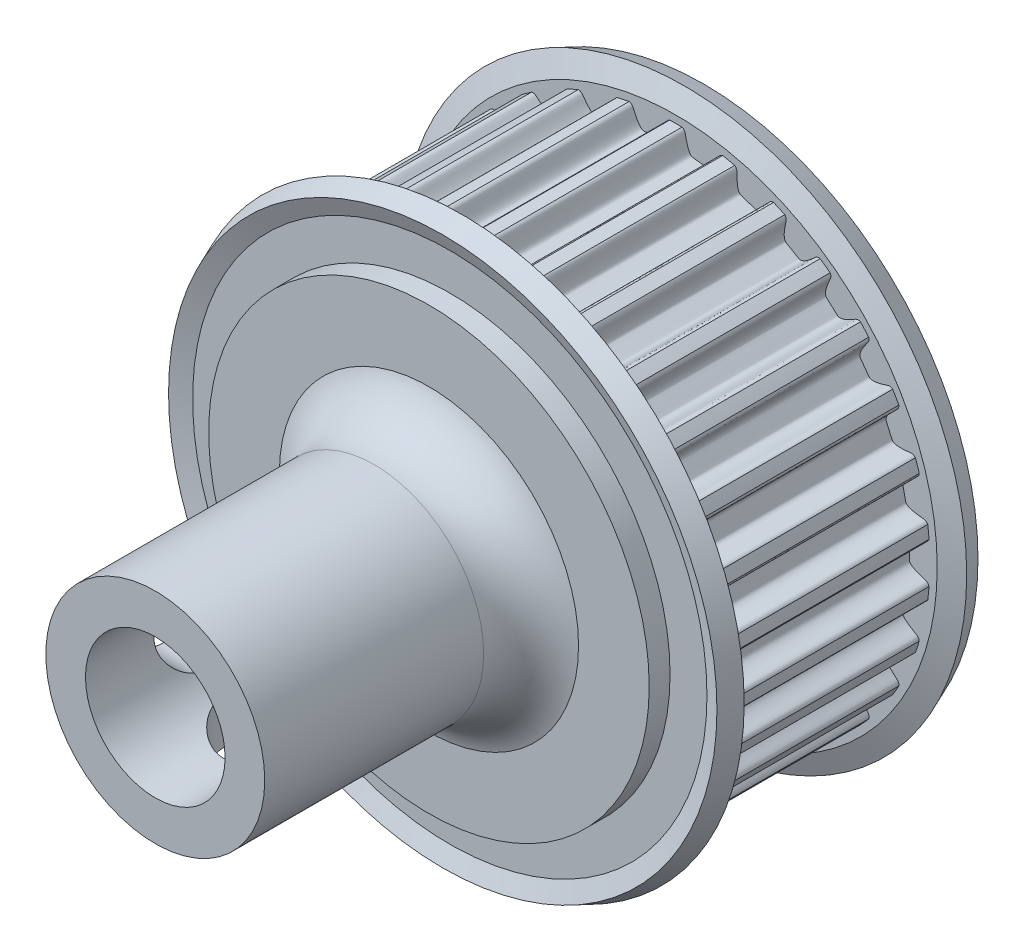
SolidWorks part; units mm, degrees
ref_plane "前视基准面" through (0, 0, 0) normal (0, 0, 1) x (1, 0, 0)
ref_plane "上视基准面" through (0, 0, 0) normal (0, 1, 0) x (1, 0, 0)
ref_plane "右视基准面" through (0, 0, 0) normal (1, 0, 0) x (0, 0, -1)
other "Configuration Table"
ref_axis "基准轴1" through (0, 0, 55) along (0, 0, -1)
sketch "SketchRevolveGearBelt01" plane through (0, 0, 0) normal (1, 0, 0) x (0, 0, -1)
  line L0 (0, 0) -> (1, 0) construction
  line L1 (5.274, 0) -> (5.274, 8.0493)
  line L2 (5.274, 8.0493) -> (4.512, 8.0493)
  line L3 (4.512, 8.0493) -> (4.512, 9.3977)
  line L4 (4.512, 9.3977) -> (4.7696, 10.0197)
  line L5 (4.7696, 10.0197) -> (4.0656, 10.3113)
  line L6 (4.0656, 10.3113) -> (3.75, 9.5493)
  line L7 (3.75, 9.5493) -> (3.75, 9.2805)
  line L8 (3.75, 9.2805) -> (-3.75, 9.2805)
  line L9 (-3.75, 9.2805) -> (-3.75, 9.5493)
  line L10 (-3.75, 9.5493) -> (-4.0656, 10.3113)
  line L11 (-4.0656, 10.3113) -> (-4.7696, 10.0197)
  line L12 (-4.7696, 10.0197) -> (-4.512, 9.3977)
  line L13 (-4.512, 9.3977) -> (-4.512, 8.0493)
  line L14 (-4.512, 8.0493) -> (-5.274, 8.0493)
  line L15 (-5.274, 8.0493) -> (-5.274, 0)
  line L16 (-5.274, 0) -> (5.274, 0)
  dimension "GearBeltFlange1OutsideLength" = 1.3484
  dimension "GearBeltFlange1X" = 0.2576
  dimension "GearBeltFlange1Y" = 0.622
  dimension "GearBeltFlangeThickness" = 0.762
  dimension "GearBeltFlangeInside" = 0.2688
  dimension "GearBeltOutsideDiameter" = 9.2805
  dimension "GearBeltFlange2X" = 0.2576
revolve "Gates_PowerGrip_GT_2mm, 6mm Belt Width" add sketch "SketchRevolveGearBelt01" angle 360 about L0
sketch "SketchToothGearBelt01" plane through (0, 0, 0) normal (0, 0, 1) x (1, 0, 0)
  arc A0 (9.2595, 0.8121) -> (9.2595, -0.8121) centre (0, 0) cw
  spline S0 degree 3 poles (9.2595, -0.8121) (9.2599, -0.7989) (9.2585, -0.7791) (9.2529, -0.7533) (9.2468, -0.7345) (9.2388, -0.7164) (9.2291, -0.6991) (9.2177, -0.6829) (9.2048, -0.6679) (9.1905, -0.6543) (9.1749, -0.6421) (9.1582, -0.6315) (9.1405, -0.6226) (9.0968, -0.6066) (9.0407, -0.5893) (8.974, -0.5675) (8.9232, -0.5498) (8.8755, -0.5322) (8.8309, -0.5145) (8.7894, -0.4969) (8.7509, -0.4793) (8.7155, -0.4616) (8.6831, -0.444) (8.6538, -0.4264) (8.6276, -0.4087) (8.6044, -0.3911) (8.5843, -0.3734) (8.5673, -0.3558) (8.5533, -0.3381) (8.5423, -0.3203) (8.5345, -0.3025) (8.5296, -0.2846) (8.5275, -0.2503) (8.5312, -0.2) (8.5317, -0.1333) (8.5327, -0.0666) (8.5328, 0) (8.5327, 0.0666) (8.5317, 0.1333) (8.5312, 0.2) (8.5275, 0.2503) (8.5296, 0.2846) (8.5345, 0.3025) (8.5423, 0.3203) (8.5533, 0.3381) (8.5673, 0.3558) (8.5843, 0.3734) (8.6044, 0.3911) (8.6276, 0.4087) (8.6538, 0.4264) (8.6831, 0.444) (8.7155, 0.4616) (8.7509, 0.4793) (8.7894, 0.4969) (8.8309, 0.5145) (8.8755, 0.5322) (8.9232, 0.5498) (8.974, 0.5675) (9.0407, 0.5893) (9.0968, 0.6066) (9.1405, 0.6226) (9.1582, 0.6315) (9.1749, 0.6421) (9.1905, 0.6543) (9.2048, 0.6679) (9.2177, 0.6829) (9.2291, 0.6991) (9.2388, 0.7164) (9.2468, 0.7345) (9.2529, 0.7533) (9.2585, 0.7791) (9.2599, 0.7989) (9.2595, 0.8121) knots 0 0 0 0 0.015924 0.023886 0.031848 0.03981 0.047771 0.055733 0.063695 0.071657 0.079619 0.087581 0.095543 0.103505 0.143783 0.166612 0.188267 0.208755 0.228086 0.24627 0.26332 0.279253 0.294087 0.307847 0.320562 0.332271 0.343022 0.352878 0.361922 0.370259 0.378023 0.385381 0.392526 0.419433 0.446289 0.473144 0.5 0.526856 0.553711 0.580567 0.607474 0.614619 0.621977 0.629741 0.638078 0.647122 0.656978 0.667729 0.679438 0.692153 0.705913 0.720747 0.73668 0.75373 0.771914 0.791245 0.811733 0.833388 0.856217 0.896495 0.904457 0.912419 0.920381 0.928343 0.936305 0.944267 0.952229 0.96019 0.968152 0.976114 0.984076 1 1 1 1
extrude "ToothExtrudeCutGearBelt01" cut sketch "SketchToothGearBelt01" against normal blind 3.75 and the other way blind 3.75
pattern_circular "Tooth Pattern, 30" count 30 every 12 about axis through (0, 0, 55) along (0, 0, -1) of "ToothExtrudeCutGearBelt01"
sketch "BoreRevolveSketch" plane through (0, 0, 0) normal (1, 0, 0) x (0, 0, -1)
  line L0 (0, 0) -> (1, 0) construction
  line L1 (-5.274, 0) -> (5.274, 0)
  line L2 (5.274, 0) -> (5.274, 5)
  line L3 (5.274, 5) -> (-5.274, 5)
  line L4 (-5.274, 5) -> (-5.274, 0)
  dimension "TaperSide1" = 5
  dimension "TaperSide2" = 5
revolve "BoreRevolveCut" cut sketch "BoreRevolveSketch" angle 360 about L0
sketch "AuxiliarySketchGearBelt01" plane through (0, 0, 0) normal (0, 0, 1) x (1, 0, 0)
  circle A0 centre (0, 0) radius 9.5493 construction
  dimension "PitchDiameter" = 19.0986
sketch "草图5" plane through (0, 0, 5.274) normal (0, 0, 1) x (1, 0, 0)
  circle A0 centre (0, 0) radius 5
extrude "凸台-拉伸1" add sketch "草图5" against normal blind 11
sketch "草图6" plane through (0, 0, 5.274) normal (0, 0, 1) x (1, 0, 0)
  circle A0 centre (0, 0) radius 2.55
  circle A1 centre (0, 0) radius 4
  dimension "D1" = 5.1
  dimension "D2" = 8
extrude "凸台-拉伸2" add sketch "草图6" along normal blind 10
sketch "草图7" plane through (0, 0, 0) normal (0, 1, 0) x (1, 0, 0)
  line L0 (-4, -5.274) -> (-4, -7.274)
  line L1 (-4, -5.274) -> (-4, -15.274) construction
  line L2 (-8.0493, -5.274) -> (8.0493, -5.274) construction
  line L3 (-5.4665, -5.274) -> (-4, -5.274)
  arc A0 (-4, -7.274) -> (-5.4665, -5.274) centre (-6.097, -7.274) ccw
  dimension "D1" = 2
revolve "旋转2" add sketch "草图7" angle 360 about axis through (0, 0, 55) along (0, 0, -1)
sketch "草图8" plane through (0, 0, 0) normal (0, 1, 0) x (1, 0, 0)
  line L0 (0, -15.274) -> (0, -11.274)
  line L1 (-4, -15.274) -> (4, -15.274) construction
  line L2 (0, -55) -> (0, 55) construction
  circle A0 centre (0, -11.274) radius 1.5
  dimension "D2" = 3
  dimension "D1" = 4
extrude "切除-拉伸2" cut sketch "草图8" against normal up to next contours A0 region at (1.0307, 0, 12.3047)
sketch "草图9" plane through (0, 0, 0) normal (1, 0, 0) x (0, 0, -1)
  line L0 (-15.274, 0) -> (-11.274, 0)
  line L1 (-15.274, 4) -> (-15.274, -4) construction
  line L2 (-55, 0) -> (55, 0) construction
  circle A0 centre (-11.274, 0) radius 1.5
  dimension "D2" = 3
  dimension "D1" = 4
extrude "切除-拉伸3" cut sketch "草图9" against normal up to next contours A0 region at (0, -1.4576, 11.274)
sketch "草图10" plane through (0, 0, 5.274) normal (0, 0, 1) x (1, 0, 0)
  circle A0 centre (0, 0) radius 2.55
extrude "切除-拉伸4" cut sketch "草图10" against normal up to next
sketch "草图11" plane through (0, 0, -5.726) normal (0, 0, -1) x (-1, 0, 0)
  circle A0 centre (0, 0) radius 8.0493
extrude "切除-拉伸5" cut sketch "草图11" against normal blind 1
